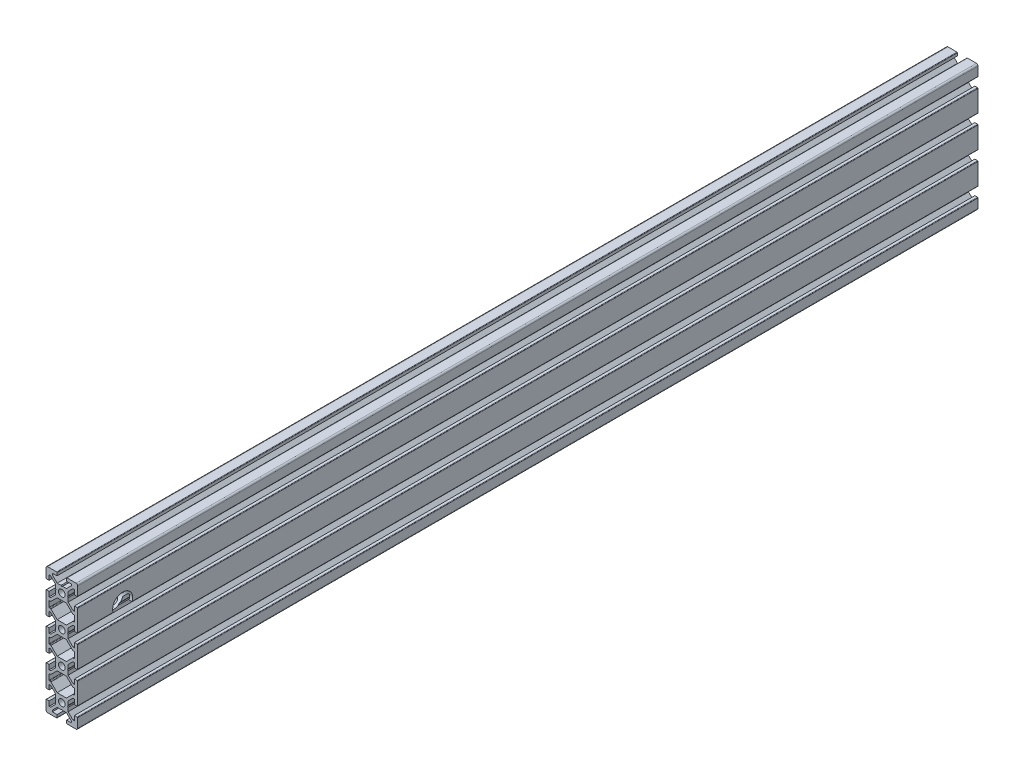
SolidWorks part; units mm, degrees
material "6063-T5"
ref_plane "Front Plane" through (0, 0, 0) normal (0, 0, 1) x (1, 0, 0)
ref_plane "Top Plane" through (0, 0, 0) normal (0, 1, 0) x (1, 0, 0)
ref_plane "Right Plane" through (0, 0, 0) normal (1, 0, 0) x (0, 0, -1)
ref_plane "Plane1" through (0, 0, 0) normal (0, 0, 1) x (1, 0, 0)
sketch "Sketch1" plane through (0, 0, 0) normal (0, 0, 1) x (1, 0, 0)
  line L0 (-9.7, -7) -> (-8, -7)
  line L1 (-8, -7) -> (-8, -4)
  line L2 (-8, -4) -> (-7.0606, -4)
  line L3 (-7.0606, -4) -> (-4, -7.0606)
  line L4 (-4, -7.0606) -> (-4, -9.4804)
  line L5 (-4, -9.4804) -> (-3.7, -10)
  line L6 (-3.7, -10) -> (-4, -10.5196)
  line L7 (-4, -10.5196) -> (-4, -12.9393)
  line L8 (-4, -12.9393) -> (-7.0607, -16)
  line L9 (-7.0607, -16) -> (-8, -16)
  line L10 (-8, -16) -> (-8, -13)
  line L11 (-8, -13) -> (-9.7, -13)
  line L12 (-10, -13.3) -> (-10, -26.7)
  line L13 (-9.7, -27) -> (-8, -27)
  line L14 (-8, -27) -> (-8, -24)
  line L15 (-8, -24) -> (-7.0606, -24)
  line L16 (-7.0606, -24) -> (-4, -27.0606)
  line L17 (-4, -27.0606) -> (-4, -29.4804)
  line L18 (-4, -29.4804) -> (-3.7, -30)
  line L19 (-3.7, -30) -> (-4, -30.5196)
  line L20 (-4, -30.5196) -> (-4, -32.9393)
  line L21 (-4, -32.9393) -> (-7.0607, -36)
  line L22 (-7.0607, -36) -> (-8, -36)
  line L23 (-8, -36) -> (-8, -33)
  line L24 (-8, -33) -> (-9.7, -33)
  line L25 (-10, -33.3) -> (-10, -39)
  line L26 (-9, -40) -> (-3.3, -40)
  line L27 (-3, -39.7) -> (-3, -38)
  line L28 (-3, -38) -> (-6, -38)
  line L29 (-6, -38) -> (-6, -37.0607)
  line L30 (-6, -37.0607) -> (-2.9393, -34)
  line L31 (-2.9393, -34) -> (-0.5196, -34)
  line L32 (-0.5196, -34) -> (0, -33.7)
  line L33 (0, -33.7) -> (0.5196, -34)
  line L34 (0.5196, -34) -> (2.9393, -34)
  line L35 (2.9393, -34) -> (6, -37.0607)
  line L36 (6, -37.0607) -> (6, -38)
  line L37 (6, -38) -> (3, -38)
  line L38 (3, -38) -> (3, -39.7)
  line L39 (3.3, -40) -> (9, -40)
  line L40 (10, -39) -> (10, -33.3)
  line L41 (9.7, -33) -> (8, -33)
  line L42 (8, -33) -> (8, -36)
  line L43 (8, -36) -> (7.0607, -36)
  line L44 (7.0607, -36) -> (4, -32.9393)
  line L45 (4, -32.9393) -> (4, -30.5196)
  line L46 (4, -30.5196) -> (3.7, -30)
  line L47 (3.7, -30) -> (4, -29.4804)
  line L48 (4, -29.4804) -> (4, -27.0606)
  line L49 (4, -27.0606) -> (7.0606, -24)
  line L50 (7.0606, -24) -> (8, -24)
  line L51 (8, -24) -> (8, -27)
  line L52 (8, -27) -> (9.7, -27)
  line L53 (10, -26.7) -> (10, -13.3)
  line L54 (9.7, -13) -> (8, -13)
  line L55 (8, -13) -> (8, -16)
  line L56 (8, -16) -> (7.0607, -16)
  line L57 (7.0607, -16) -> (4, -12.9393)
  line L58 (4, -12.9393) -> (4, -10.5196)
  line L59 (4, -10.5196) -> (3.7, -10)
  line L60 (3.7, -10) -> (4, -9.4804)
  line L61 (4, -9.4804) -> (4, -7.0606)
  line L62 (4, -7.0606) -> (7.0606, -4)
  line L63 (7.0606, -4) -> (8, -4)
  line L64 (8, -4) -> (8, -7)
  line L65 (8, -7) -> (9.7, -7)
  line L66 (10, -6.7) -> (10, 6.7)
  line L67 (9.7, 7) -> (8, 7)
  line L68 (8, 7) -> (8, 4)
  line L69 (8, 4) -> (7.0606, 4)
  line L70 (7.0606, 4) -> (4, 7.0606)
  line L71 (4, 7.0606) -> (4, 9.4804)
  line L72 (4, 9.4804) -> (3.7, 10)
  line L73 (3.7, 10) -> (4, 10.5196)
  line L74 (4, 10.5196) -> (4, 12.9393)
  line L75 (4, 12.9393) -> (7.0607, 16)
  line L76 (7.0607, 16) -> (8, 16)
  line L77 (8, 16) -> (8, 13)
  line L78 (8, 13) -> (9.7, 13)
  line L79 (10, 13.3) -> (10, 26.7)
  line L80 (9.7, 27) -> (8, 27)
  line L81 (8, 27) -> (8, 24)
  line L82 (8, 24) -> (7.0606, 24)
  line L83 (7.0606, 24) -> (4, 27.0606)
  line L84 (4, 27.0606) -> (4, 29.4804)
  line L85 (4, 29.4804) -> (3.7, 30)
  line L86 (3.7, 30) -> (4, 30.5196)
  line L87 (4, 30.5196) -> (4, 32.9393)
  line L88 (4, 32.9393) -> (7.0607, 36)
  line L89 (7.0607, 36) -> (8, 36)
  line L90 (8, 36) -> (8, 33)
  line L91 (8, 33) -> (9.7, 33)
  line L92 (10, 33.3) -> (10, 39)
  line L93 (9, 40) -> (3.3, 40)
  line L94 (3, 39.7) -> (3, 38)
  line L95 (3, 38) -> (6, 38)
  line L96 (6, 38) -> (6, 37.0607)
  line L97 (6, 37.0607) -> (2.9393, 34)
  line L98 (2.9393, 34) -> (0.5196, 34)
  line L99 (0.5196, 34) -> (0, 33.7)
  line L100 (0, 33.7) -> (-0.5196, 34)
  line L101 (-0.5196, 34) -> (-2.9393, 34)
  line L102 (-2.9393, 34) -> (-6, 37.0607)
  line L103 (-6, 37.0607) -> (-6, 38)
  line L104 (-6, 38) -> (-3, 38)
  line L105 (-3, 38) -> (-3, 39.7)
  line L106 (-3.3, 40) -> (-9, 40)
  line L107 (-10, 39) -> (-10, 33.3)
  line L108 (-9.7, 33) -> (-8, 33)
  line L109 (-8, 33) -> (-8, 36)
  line L110 (-8, 36) -> (-7.0607, 36)
  line L111 (-7.0607, 36) -> (-4, 32.9393)
  line L112 (-4, 32.9393) -> (-4, 30.5196)
  line L113 (-4, 30.5196) -> (-3.7, 30)
  line L114 (-3.7, 30) -> (-4, 29.4804)
  line L115 (-4, 29.4804) -> (-4, 27.0606)
  line L116 (-4, 27.0606) -> (-7.0606, 24)
  line L117 (-7.0606, 24) -> (-8, 24)
  line L118 (-8, 24) -> (-8, 27)
  line L119 (-8, 27) -> (-9.7, 27)
  line L120 (-10, 26.7) -> (-10, 13.3)
  line L121 (-9.7, 13) -> (-8, 13)
  line L122 (-8, 13) -> (-8, 16)
  line L123 (-8, 16) -> (-7.0607, 16)
  line L124 (-7.0607, 16) -> (-4, 12.9393)
  line L125 (-4, 12.9393) -> (-4, 10.5196)
  line L126 (-4, 10.5196) -> (-3.7, 10)
  line L127 (-3.7, 10) -> (-4, 9.4804)
  line L128 (-4, 9.4804) -> (-4, 7.0606)
  line L129 (-4, 7.0606) -> (-7.0606, 4)
  line L130 (-7.0606, 4) -> (-8, 4)
  line L131 (-8, 4) -> (-8, 7)
  line L132 (-8, 7) -> (-9.7, 7)
  line L133 (-10, 6.7) -> (-10, -6.7)
  line L134 (-7.7, -2) -> (-7.0636, -2)
  line L135 (-6.8515, -2.0878) -> (-2.9393, -6)
  line L136 (-2.9393, -6) -> (2.9393, -6)
  line L137 (2.9393, -6) -> (6.8515, -2.0878)
  line L138 (7.0636, -2) -> (7.7, -2)
  line L139 (8, -1.7) -> (8, 1.7)
  line L140 (7.7, 2) -> (7.0636, 2)
  line L141 (6.8515, 2.0878) -> (2.9393, 6)
  line L142 (2.9393, 6) -> (-2.9393, 6)
  line L143 (-2.9393, 6) -> (-6.8515, 2.0878)
  line L144 (-7.0636, 2) -> (-7.7, 2)
  line L145 (-8, 1.7) -> (-8, -1.7)
  line L146 (-8, 21.7) -> (-8, 18.2999)
  line L147 (-7.7, 18) -> (-7.0636, 18)
  line L148 (-6.8515, 17.9121) -> (-2.9394, 14)
  line L149 (-2.9394, 14) -> (2.9394, 14)
  line L150 (2.9394, 14) -> (6.8515, 17.9121)
  line L151 (7.0636, 18) -> (7.7, 18)
  line L152 (8, 18.2999) -> (8, 21.7)
  line L153 (7.7, 22) -> (7.0636, 22)
  line L154 (6.8515, 22.0878) -> (2.9393, 26)
  line L155 (2.9393, 26) -> (-2.9393, 26)
  line L156 (-2.9393, 26) -> (-6.8515, 22.0878)
  line L157 (-7.0636, 22) -> (-7.7, 22)
  line L158 (-8, -18.2999) -> (-8, -21.7)
  line L159 (-7.7, -22) -> (-7.0636, -22)
  line L160 (-6.8515, -22.0878) -> (-2.9393, -26)
  line L161 (-2.9393, -26) -> (2.9393, -26)
  line L162 (2.9393, -26) -> (6.8515, -22.0878)
  line L163 (7.0636, -22) -> (7.7, -22)
  line L164 (8, -21.7) -> (8, -18.2999)
  line L165 (7.7, -18) -> (7.0636, -18)
  line L166 (6.8515, -17.9121) -> (2.9394, -14)
  line L167 (2.9394, -14) -> (-2.9394, -14)
  line L168 (-2.9394, -14) -> (-6.8515, -17.9121)
  line L169 (-7.0636, -18) -> (-7.7, -18)
  arc A0 (-10, -6.7) -> (-9.7, -7) centre (-9.7, -6.7) ccw
  arc A1 (-9.7, -13) -> (-10, -13.3) centre (-9.7, -13.3) ccw
  arc A2 (-10, -26.7) -> (-9.7, -27) centre (-9.7, -26.7) ccw
  arc A3 (-9.7, -33) -> (-10, -33.3) centre (-9.7, -33.3) ccw
  arc A4 (-10, -39) -> (-9, -40) centre (-9, -39) ccw
  arc A5 (-3.3, -40) -> (-3, -39.7) centre (-3.3, -39.7) ccw
  arc A6 (3, -39.7) -> (3.3, -40) centre (3.3, -39.7) ccw
  arc A7 (9, -40) -> (10, -39) centre (9, -39) ccw
  arc A8 (10, -33.3) -> (9.7, -33) centre (9.7, -33.3) ccw
  arc A9 (9.7, -27) -> (10, -26.7) centre (9.7, -26.7) ccw
  arc A10 (10, -13.3) -> (9.7, -13) centre (9.7, -13.3) ccw
  arc A11 (9.7, -7) -> (10, -6.7) centre (9.7, -6.7) ccw
  arc A12 (10, 6.7) -> (9.7, 7) centre (9.7, 6.7) ccw
  arc A13 (9.7, 13) -> (10, 13.3) centre (9.7, 13.3) ccw
  arc A14 (10, 26.7) -> (9.7, 27) centre (9.7, 26.7) ccw
  arc A15 (9.7, 33) -> (10, 33.3) centre (9.7, 33.3) ccw
  arc A16 (10, 39) -> (9, 40) centre (9, 39) ccw
  arc A17 (3.3, 40) -> (3, 39.7) centre (3.3, 39.7) ccw
  arc A18 (-3, 39.7) -> (-3.3, 40) centre (-3.3, 39.7) ccw
  arc A19 (-9, 40) -> (-10, 39) centre (-9, 39) ccw
  arc A20 (-10, 33.3) -> (-9.7, 33) centre (-9.7, 33.3) ccw
  arc A21 (-9.7, 27) -> (-10, 26.7) centre (-9.7, 26.7) ccw
  arc A22 (-10, 13.3) -> (-9.7, 13) centre (-9.7, 13.3) ccw
  arc A23 (-9.7, 7) -> (-10, 6.7) centre (-9.7, 6.7) ccw
  circle A24 centre (0, 30) radius 2.1
  circle A25 centre (0, 10) radius 2.1
  circle A26 centre (0, -10) radius 2.1
  circle A27 centre (0, -30) radius 2.1
  arc A28 (-8, -1.7) -> (-7.7, -2) centre (-7.7, -1.7) ccw
  arc A29 (-7.0636, -2) -> (-6.8515, -2.0878) centre (-7.0633, -2.2994) cw
  arc A30 (6.8515, -2.0878) -> (7.0636, -2) centre (7.0633, -2.2994) cw
  arc A31 (7.7, -2) -> (8, -1.7) centre (7.7, -1.7) ccw
  arc A32 (8, 1.7) -> (7.7, 2) centre (7.7, 1.7) ccw
  arc A33 (7.0636, 2) -> (6.8515, 2.0878) centre (7.0633, 2.2994) cw
  arc A34 (-6.8515, 2.0878) -> (-7.0636, 2) centre (-7.0633, 2.2994) cw
  arc A35 (-7.7, 2) -> (-8, 1.7) centre (-7.7, 1.7) ccw
  arc A36 (-8, 18.2999) -> (-7.7, 18) centre (-7.7001, 18.2999) ccw
  arc A37 (-7.0636, 18) -> (-6.8515, 17.9121) centre (-7.0638, 17.6996) cw
  arc A38 (6.8515, 17.9121) -> (7.0636, 18) centre (7.0638, 17.6996) cw
  arc A39 (7.7, 18) -> (8, 18.2999) centre (7.7001, 18.2999) ccw
  arc A40 (8, 21.7) -> (7.7, 22) centre (7.6999, 21.6999) ccw
  arc A41 (7.0636, 22) -> (6.8515, 22.0878) centre (7.0633, 22.2993) cw
  arc A42 (-6.8515, 22.0878) -> (-7.0636, 22) centre (-7.0633, 22.2993) cw
  arc A43 (-7.7, 22) -> (-8, 21.7) centre (-7.6999, 21.6999) ccw
  arc A44 (-8, -21.7) -> (-7.7, -22) centre (-7.6999, -21.6999) ccw
  arc A45 (-7.0636, -22) -> (-6.8515, -22.0878) centre (-7.0633, -22.2993) cw
  arc A46 (6.8515, -22.0878) -> (7.0636, -22) centre (7.0633, -22.2993) cw
  arc A47 (7.7, -22) -> (8, -21.7) centre (7.6999, -21.6999) ccw
  arc A48 (8, -18.2999) -> (7.7, -18) centre (7.7001, -18.2999) ccw
  arc A49 (7.0636, -18) -> (6.8515, -17.9121) centre (7.0638, -17.6996) cw
  arc A50 (-6.8515, -17.9121) -> (-7.0636, -18) centre (-7.0638, -17.6996) cw
  arc A51 (-7.7, -18) -> (-8, -18.2999) centre (-7.7001, -18.2999) ccw
extrude "Boss-Extrude1" add sketch "Sketch1" against normal blind 569.5
sketch "Sketch2" [suppressed] plane through (10, 0, 0) normal (1, 0, 0) x (0, 0, -1)
  line L0 (569.5, 13.3) -> (569.5, 26.7) construction
  line L1 (569.5, 40) -> (0, 40) construction
  circle A0 centre (531, 15) radius 6.35
  dimension "D1" = 38.5
  dimension "D2" = 25
  dimension "D3" = 12.7
extrude "Cut-Extrude1" [suppressed] cut sketch "Sketch2" against normal up to surface (20 mm away) up to face at (-10, 20, -284.75)
sketch "Sketch3" plane through (10, 0, 0) normal (1, 0, 0) x (0, 0, -1)
  line L0 (569.5, 40) -> (0, 40) construction
  line L1 (0, 13.3) -> (0, 26.7) construction
  circle A0 centre (28.5, 15) radius 6.35
  dimension "D1" = 25
  dimension "D2" = 28.5
  dimension "D3" = 12.7
extrude "Cut-Extrude2" cut sketch "Sketch3" against normal up to surface (20 mm away) up to face at (-10, 20, -284.75)
sketch "Sketch4" [suppressed] plane through (10, 0, 0) normal (1, 0, 0) x (0, 0, -1)
  line L0 (284.75, 40) -> (284.75, -40) construction
  line L1 (569.5, 40) -> (0, 40) construction
  line L2 (569.5, -40) -> (0, -40) construction
  line L3 (0, -6.7) -> (0, 6.7) construction
  line L4 (0, -26.7) -> (0, -13.3) construction
  circle A0 centre (38.5, -5) radius 6.35
  circle A1 centre (531, -5) radius 6.35
  circle A2 centre (225, -30) radius 2.5
  circle A3 centre (245, -30) radius 2.5
  circle A4 centre (265, -30) radius 2.5
  circle A5 centre (285, -30) radius 2.5
  dimension "D1" = 12.7
  dimension "D2" = 45
  dimension "D3" = 38.5
  dimension "D4" = 5
  dimension "D5" = 10
  dimension "D6" = 225
  dimension "D8" = 20
  dimension "D7" = 4
extrude "Cut-Extrude3" [suppressed] cut sketch "Sketch4" against normal up to surface (20 mm away) up to face at (-10, 0, -284.75)
sketch "Sketch5" [suppressed] plane through (10, 0, 0) normal (1, 0, 0) x (0, 0, -1)
  line L0 (0, 13.3) -> (0, 26.7) construction
  line L1 (569.5, 40) -> (0, 40) construction
  circle A0 centre (225, 30) radius 2.5
  circle A1 centre (245, 30) radius 2.5
  circle A2 centre (265, 30) radius 2.5
  circle A3 centre (285, 30) radius 2.5
  circle A4 centre (225, 10) radius 2.5
  circle A5 centre (245, 10) radius 2.5
  circle A6 centre (265, 10) radius 2.5
  circle A7 centre (285, 10) radius 2.5
  dimension "D1" = 5
  dimension "D2" = 225
  dimension "D3" = 10
  dimension "D5" = 20
  dimension "D7" = 20
  dimension "D4" = 4
  dimension "D6" = 2
extrude "Cut-Extrude4" [suppressed] cut sketch "Sketch5" against normal up to surface (20 mm away) up to face at (-10, 19.1083, -199.3333)
sketch "Sketch6" [suppressed] plane through (10, 0, 0) normal (1, 0, 0) x (0, 0, -1)
  line L0 (569.5, -40) -> (0, -40) construction
  line L1 (0, -26.7) -> (0, -13.3) construction
  circle A0 centre (225, -30) radius 2.5
  circle A1 centre (245, -30) radius 2.5
  circle A2 centre (265, -30) radius 2.5
  circle A3 centre (285, -30) radius 2.5
  dimension "D1" = 5
  dimension "D2" = 10
  dimension "D3" = 225
  dimension "D5" = 20
  dimension "D4" = 4
extrude "Cut-Extrude5" [suppressed] cut sketch "Sketch6" against normal up to surface (20 mm away) up to face at (-10, 0, -284.75)
